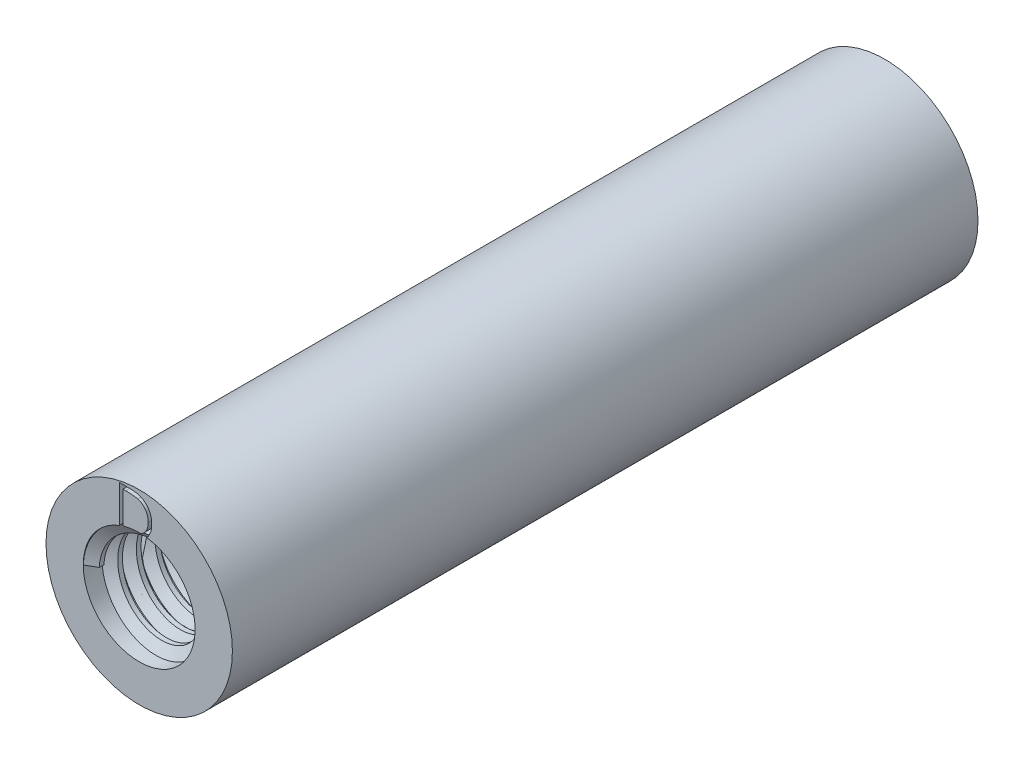
SolidWorks part; units mm, degrees
ref_plane "Plan de face" through (0, 0, 0) normal (0, 0, 1) x (1, 0, 0)
ref_plane "Plan de dessus" through (0, 0, 0) normal (0, 1, 0) x (1, 0, 0)
ref_plane "Plan de droite" through (0, 0, 0) normal (1, 0, 0) x (0, 0, -1)
sketch "Esquisse1" plane through (0, 0, 0) normal (0, 0, 1) x (1, 0, 0)
  circle A0 centre (0, 0) radius 5
  circle A1 centre (0, 0) radius 3
  dimension "D1" = 10
extrude "Boss.-Extru.1" add sketch "Esquisse1" along normal blind 40
thread "Filetage1" pitch 1 start angle 0, offset 0, length 20, pitch 1, diameter 6
ref_plane "Plan1" through (-3, 0, 40) normal (0, -1, 0) x (-1, 0, 0)
sketch "Profil de filetage1" plane through (-3, 0, 40) normal (0, -1, 0) x (-1, 0, 0)
  line L0 (0, 0) -> (0, 1) construction
  line L11 (0, 0) -> (0, 0.875)
  line L12 (0, 0.875) -> (-0.5413, 0.5625)
  line L13 (-0.5413, 0.5625) -> (-0.5413, 0.3125)
  line L15 (-0.5413, 0.3125) -> (0, 0)
  line L17 (-0.5413, 0.4375) -> (0, 0.4375) construction
  point P2 (0, 0)
  dimension "Pitch" = 1
  dimension "Profile_Angle" = 60
  dimension "Profile_Land" = 0.25
  dimension "Profile_Height" = 0.5413
thread "Filetage2" start angle 0, offset 0, length 20, pitch 1, diameter 6
ref_plane "Plan2" through (3, 0, 0) normal (0, -1, 0) x (1, 0, 0)
sketch "Profil de filetage2" plane through (3, 0, 0) normal (0, -1, 0) x (1, 0, 0)
  line L0 (0, 0) -> (0, 1) construction
  line L11 (0, 0) -> (0, 0.875)
  line L12 (0, 0.875) -> (-0.5413, 0.5625)
  line L13 (-0.5413, 0.5625) -> (-0.5413, 0.3125)
  line L15 (-0.5413, 0.3125) -> (0, 0)
  line L17 (-0.5413, 0.4375) -> (0, 0.4375) construction
  point P2 (0, 0)
  dimension "Pitch" = 1
  dimension "Profile_Angle" = 60
  dimension "Profile_Land" = 0.25
  dimension "Profile_Height" = 0.5413
sketch "Esquisse6" plane through (0, 0, 0) normal (0, 0, -1) x (-1, 0, 0)
  circle A0 centre (0, 0) radius 3 construction
  text T0 "G" font "Century Gothic" height in points 8
extrude "Enlèv. mat.-Extru.1" cut sketch "Esquisse6" against normal blind 1
sketch "Esquisse7" plane through (0, 0, 40) normal (0, 0, 1) x (1, 0, 0)
  circle A0 centre (0, 0) radius 3 construction
  text T0 "D" font "Century Gothic" height in points 8
extrude "Enlèv. mat.-Extru.2" cut sketch "Esquisse7" against normal blind 1
